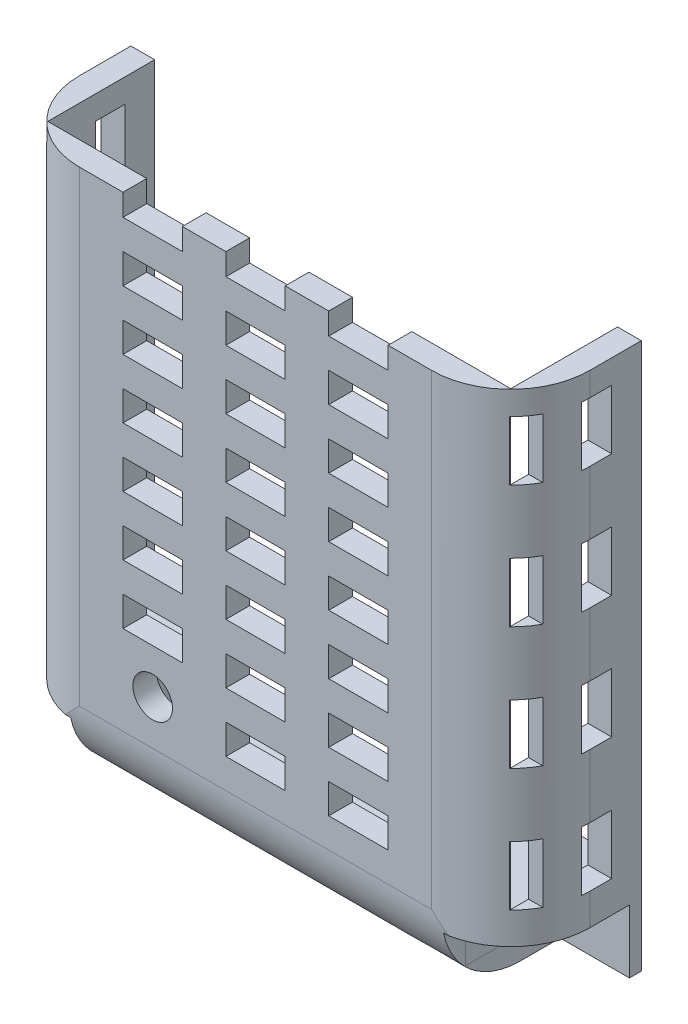
SolidWorks part; units mm, degrees
ref_plane "Plano frontal" through (0, 0, 0) normal (0, 0, 1) x (1, 0, 0)
ref_plane "Plano superior" through (0, 0, 0) normal (0, 1, 0) x (1, 0, 0)
ref_plane "Plano direito" through (0, 0, 0) normal (1, 0, 0) x (0, 0, -1)
sketch "Esboço1" plane through (0, 0, 0) normal (0, 0, 1) x (1, 0, 0)
  line L0 (-47.125, -132) -> (-47.125, -122)
  line L1 (-64.5, 138) -> (64.5, 138)
  line L2 (-64.5, 138) -> (-64.5, -138)
  line L3 (-64.5, -138) -> (64.5, -138)
  line L4 (64.5, 138) -> (64.5, -138)
  line L5 (0, -138) -> (0, 138) construction
  line L6 (-64.5, 0) -> (64.5, 0) construction
  line L7 (-58.5, 132) -> (58.5, 132) construction
  line L8 (-58.5, 132) -> (-58.5, -132) construction
  line L9 (-58.5, -132) -> (58.5, -132) construction
  line L10 (58.5, 132) -> (58.5, -132) construction
  line L11 (0, -132) -> (0, 132) construction
  line L12 (-58.5, 0) -> (58.5, 0) construction
  line L13 (-47.125, -122) -> (-58.5, -122)
  line L14 (-47, 132) -> (-47, 124.5)
  line L15 (-47, 124.5) -> (-35, 124.5)
  line L16 (-35, 124.5) -> (-35, 132)
  line L17 (-41, 130.5) -> (-41, 124.5) construction
  line L18 (-41, 130.5) -> (-35, 130.5) construction
  line L19 (-47, 132) -> (-58.5, 132)
  line L20 (-58.5, 132) -> (-58.5, -122)
  line L21 (41, 130.5) -> (35, 130.5) construction
  line L22 (41, 130.5) -> (41, 124.5) construction
  line L23 (47, 132) -> (58.5, 132)
  line L24 (35, 124.5) -> (35, 132)
  line L25 (47, 124.5) -> (35, 124.5)
  line L26 (47, 132) -> (47, 124.5)
  line L27 (58.5, 132) -> (58.5, -132) construction
  line L28 (58.5, 132) -> (58.5, -122)
  line L29 (47.125, -122) -> (58.5, -122)
  line L30 (47.125, -132) -> (47.125, -122)
  line L31 (-35, 132) -> (35, 132)
  line L32 (47.125, -132) -> (-47.125, -132)
  circle A0 centre (-53.125, -128) radius 1.6
  circle A1 centre (-41, 130.5) radius 1.6
  circle A2 centre (41, 130.5) radius 1.6
  circle A3 centre (53.125, -128) radius 1.6
  point P56 (0, 0)
  point P83 (0, 0)
  dimension "D5" = 3.2
  dimension "D8" = 3.2
  dimension "D1" = 129
  dimension "D2" = 276
  dimension "D3" = 6
  dimension "D4" = 6
  dimension "D6" = 11.375
  dimension "D7" = 10
  dimension "D9" = 23.5
  dimension "D10" = 7.5
  dimension "D11" = 6
  dimension "D12" = 6
  dimension "D13" = 6
extrude "Ressalto-extrusão1" add sketch "Esboço1" along normal blind 3
sketch "Esboço4" plane through (0, 0, 3) normal (0, 0, 1) x (1, 0, 0)
  line L0 (-64.5, 138) -> (-64.5, 72)
  line L1 (-64.5, 138) -> (-64.5, -138) construction
  line L2 (-64.5, 72) -> (-58.5, 72)
  line L3 (-58.5, 132) -> (-58.5, -122) construction
  line L4 (-58.5, 72) -> (-58.5, 132)
  line L5 (-58.5, 132) -> (-47, 132)
  line L6 (-47, 132) -> (-47, 138)
  line L7 (64.5, 138) -> (-64.5, 138) construction
  line L8 (-47, 138) -> (-64.5, 138)
  line L9 (-35, 132) -> (-35, 138)
  line L10 (-35, 138) -> (35, 138)
  line L11 (35, 138) -> (35, 132)
  line L12 (35, 132) -> (-35, 132)
  line L13 (47, 132) -> (47, 138)
  line L14 (47, 138) -> (64.5, 138)
  line L15 (64.5, 138) -> (64.5, 72)
  line L16 (64.5, -138) -> (64.5, 138) construction
  line L17 (64.5, 72) -> (58.5, 72)
  line L18 (58.5, -122) -> (58.5, 132) construction
  line L19 (58.5, 72) -> (58.5, 132)
  line L20 (58.5, 132) -> (47, 132)
  line L21 (-47.125, -132) -> (-47.125, -138)
  line L22 (-64.5, -138) -> (64.5, -138) construction
  line L23 (-47.125, -138) -> (47, -138)
  line L24 (47, -138) -> (47.125, -132)
  line L25 (47.125, -132) -> (-47.125, -132)
  line L26 (-58.5, -122) -> (-64.5, -122)
  line L27 (-64.5, -122) -> (-64.5, -22)
  line L28 (-64.5, -22) -> (-58.5, -22)
  line L29 (-58.5, -22) -> (-58.5, -122)
  line L30 (58.5, -122) -> (64.5, -122)
  line L31 (64.5, -122) -> (64.5, -22)
  line L32 (64.5, -22) -> (58.5, -22)
  line L33 (58.5, -22) -> (58.5, -122)
  dimension "D1" = 60
  dimension "D2" = 100
extrude "Ressalto-extrusão2" add sketch "Esboço4" along normal blind 24
sketch "Esboço5" plane through (0, 0, 27) normal (0, 0, 1) x (1, 0, 0)
  line L0 (-35, 132) -> (-35, 138)
  line L1 (-35, 138) -> (35, 138)
  line L2 (35, 138) -> (35, 132)
  line L3 (47, 132) -> (47, 138)
  line L4 (47, 138) -> (64.5, 138)
  line L5 (64.5, 138) -> (64.5, 72)
  line L6 (64.5, 72) -> (58.5, 72)
  line L7 (58.5, 72) -> (-64.5, 72)
  line L8 (-64.5, 72) -> (-64.5, 138)
  line L9 (-64.5, 138) -> (-47, 138)
  line L10 (-47, 138) -> (-47, 124.5)
  line L11 (-47, 124.5) -> (-35, 124.5)
  line L12 (-35, 124.5) -> (-35, 132)
  line L13 (35, 132) -> (35, 124.5)
  line L14 (35, 124.5) -> (47, 124.5)
  line L15 (47, 124.5) -> (47, 132)
  line L16 (-47.125, -138) -> (47, -138)
  line L17 (47, -138) -> (47.125, -122)
  line L18 (47.125, -122) -> (64.5, -122)
  line L19 (64.5, -122) -> (64.5, -22)
  line L20 (64.5, -22) -> (-64.5, -22)
  line L21 (-64.5, -22) -> (-64.5, -122)
  line L22 (-64.5, -122) -> (-47.125, -122)
  line L23 (-47.125, -122) -> (-47.125, -138)
extrude "Ressalto-extrusão3" add sketch "Esboço5" along normal blind 6
sketch "Esboço7" plane through (0, 0, 27) normal (0, 0, -1) x (-1, 0, 0)
  line L0 (-47, 132) -> (-53, 132)
  line L1 (-47, 132) -> (-58.5, 132) construction
  line L2 (-53, 132) -> (-53, 118.5)
  line L3 (-53, 118.5) -> (-29, 118.5)
  line L4 (-29, 118.5) -> (-29, 132)
  line L5 (35, 132) -> (-35, 132) construction
  line L6 (-29, 132) -> (-35, 132)
  line L7 (-35, 132) -> (-35, 124.5)
  line L8 (-35, 124.5) -> (-47, 124.5)
  line L9 (-47, 132) -> (-47, 124.5) construction
  line L10 (-47, 124.5) -> (-35, 124.5) construction
  line L11 (-47, 124.5) -> (-47, 132)
  line L19 (0, 0) -> (0, 50000) construction
  line L20 (58.5, -122) -> (58.5, -22) construction
  line L27 (47.125, -132) -> (47.125, -122)
  line L28 (47.125, -122) -> (58.5, -122)
  line L29 (58.5, -122) -> (58.5, -116)
  line L30 (58.5, -116) -> (41.125, -116)
  line L31 (41.125, -116) -> (41.125, -132)
  line L32 (-47.0469, -132) -> (47.125, -132) construction
  line L33 (41.125, -132) -> (47.125, -132)
  line L34 (47, 124.5) -> (47, 132)
  line L35 (35, 124.5) -> (47, 124.5)
  line L36 (35, 132) -> (35, 124.5)
  line L37 (29, 132) -> (35, 132)
  line L38 (29, 118.5) -> (29, 132)
  line L39 (53, 118.5) -> (29, 118.5)
  line L40 (53, 132) -> (53, 118.5)
  line L41 (47, 132) -> (53, 132)
  line L42 (-41.125, -132) -> (-47.125, -132)
  line L43 (-41.125, -116) -> (-41.125, -132)
  line L44 (-58.5, -116) -> (-41.125, -116)
  line L45 (-58.5, -122) -> (-58.5, -116)
  line L46 (-47.125, -122) -> (-58.5, -122)
  line L47 (-47.125, -132) -> (-47.125, -122)
  dimension "D1" = 6
  dimension "D2" = 6
  dimension "D5" = 6
extrude "Ressalto-extrusão5" add sketch "Esboço7" along normal up to vertex (27 mm away) up to point (35, 124.5, 0)
sketch "Esboço8" plane through (0, -22, 0) normal (0, 1, 0) x (1, 0, 0)
  line L0 (-58.5, -3) -> (-64.5, -3)
  line L1 (-64.5, -3) -> (-64.5, -33)
  line L2 (-64.5, -33) -> (64.5, -33)
  line L3 (64.5, -33) -> (64.5, -3)
  line L4 (64.5, -3) -> (58.5, -3)
  line L5 (58.5, -3) -> (58.5, -27)
  line L6 (58.5, -27) -> (-58.5, -27)
  line L7 (-58.5, -27) -> (-58.5, -3)
extrude "Ressalto-extrusão6" add sketch "Esboço8" along normal up to vertex (94 mm away) up to point (-58.5, 72, 27)
fillet "Filete1" radius 20 4 edges at (0, 138, 33) (-0.0625, -138, 33) (64.5, 8, 33) (-64.5, 8, 33)
sketch "Esboço9" plane through (0, 0, 33) normal (0, 0, 1) x (1, 0, 0)
  line L2 (-18.5, -106.75) -> (-7.5, -106.75) construction
  line L7 (-33.5, -103) -> (-18.5, -103) construction
  line L8 (-33.5, -103) -> (-33.5, -110.5) construction
  line L9 (-33.5, -110.5) -> (-18.5, -110.5) construction
  line L10 (-18.5, -103) -> (-18.5, -110.5) construction
  line L11 (-26, -110.5) -> (-26, -103) construction
  line L12 (-33.5, -106.75) -> (-18.5, -106.75) construction
  line L13 (-7.5, -103) -> (7.5, -103)
  line L14 (-7.5, -103) -> (-7.5, -110.5)
  line L15 (-7.5, -110.5) -> (7.5, -110.5)
  line L16 (7.5, -103) -> (7.5, -110.5)
  line L17 (0, -110.5) -> (0, -103) construction
  line L18 (-7.5, -106.75) -> (7.5, -106.75) construction
  line L19 (18.5, -103) -> (33.5, -103)
  line L20 (18.5, -103) -> (18.5, -110.5)
  line L21 (18.5, -110.5) -> (33.5, -110.5)
  line L22 (33.5, -103) -> (33.5, -110.5)
  line L23 (26, -110.5) -> (26, -103) construction
  line L24 (18.5, -106.75) -> (33.5, -106.75) construction
  line L25 (7.5, -106.75) -> (18.5, -106.75) construction
  line L26 (-33.5, -106.75) -> (-44.5, -106.75) construction
  line L27 (-44.5, 118) -> (-44.5, -118) construction
  line L28 (33.5, -106.75) -> (44.5, -106.75) construction
  line L29 (44.5, -118) -> (44.5, 118) construction
  line L30 (-44.5, -118) -> (44.5, -118) construction
  line L31 (-33.5, -88) -> (-18.5, -88)
  line L32 (-33.5, -88) -> (-33.5, -95.5)
  line L33 (-33.5, -95.5) -> (-18.5, -95.5)
  line L34 (-18.5, -88) -> (-18.5, -95.5)
  line L35 (-7.5, -88) -> (7.5, -88)
  line L36 (-7.5, -88) -> (-7.5, -95.5)
  line L37 (-7.5, -95.5) -> (7.5, -95.5)
  line L38 (7.5, -88) -> (7.5, -95.5)
  line L39 (18.5, -88) -> (33.5, -88)
  line L40 (18.5, -88) -> (18.5, -95.5)
  line L41 (18.5, -95.5) -> (33.5, -95.5)
  line L42 (33.5, -88) -> (33.5, -95.5)
  line L43 (-18.5, -91.75) -> (-7.5, -91.75) construction
  line L44 (-26, -95.5) -> (-26, -88) construction
  line L45 (-33.5, -91.75) -> (-18.5, -91.75) construction
  line L46 (0, -95.5) -> (0, -88) construction
  line L47 (-7.5, -91.75) -> (7.5, -91.75) construction
  line L48 (26, -95.5) -> (26, -88) construction
  line L49 (18.5, -91.75) -> (33.5, -91.75) construction
  line L50 (7.5, -91.75) -> (18.5, -91.75) construction
  line L51 (-33.5, -73) -> (-18.5, -73)
  line L52 (-33.5, -73) -> (-33.5, -80.5)
  line L53 (-33.5, -80.5) -> (-18.5, -80.5)
  line L54 (-18.5, -73) -> (-18.5, -80.5)
  line L55 (-7.5, -73) -> (7.5, -73)
  line L56 (-7.5, -73) -> (-7.5, -80.5)
  line L57 (-7.5, -80.5) -> (7.5, -80.5)
  line L58 (7.5, -73) -> (7.5, -80.5)
  line L59 (18.5, -73) -> (33.5, -73)
  line L60 (18.5, -73) -> (18.5, -80.5)
  line L61 (18.5, -80.5) -> (33.5, -80.5)
  line L62 (33.5, -73) -> (33.5, -80.5)
  line L63 (-18.5, -76.75) -> (-7.5, -76.75) construction
  line L64 (-26, -80.5) -> (-26, -73) construction
  line L65 (-33.5, -76.75) -> (-18.5, -76.75) construction
  line L66 (0, -80.5) -> (0, -73) construction
  line L67 (-7.5, -76.75) -> (7.5, -76.75) construction
  line L68 (26, -80.5) -> (26, -73) construction
  line L69 (18.5, -76.75) -> (33.5, -76.75) construction
  line L70 (7.5, -76.75) -> (18.5, -76.75) construction
  line L71 (-33.5, -58) -> (-18.5, -58)
  line L72 (-33.5, -58) -> (-33.5, -65.5)
  line L73 (-33.5, -65.5) -> (-18.5, -65.5)
  line L74 (-18.5, -58) -> (-18.5, -65.5)
  line L75 (-7.5, -58) -> (7.5, -58)
  line L76 (-7.5, -58) -> (-7.5, -65.5)
  line L77 (-7.5, -65.5) -> (7.5, -65.5)
  line L78 (7.5, -58) -> (7.5, -65.5)
  line L79 (18.5, -58) -> (33.5, -58)
  line L80 (18.5, -58) -> (18.5, -65.5)
  line L81 (18.5, -65.5) -> (33.5, -65.5)
  line L82 (33.5, -58) -> (33.5, -65.5)
  line L83 (-18.5, -61.75) -> (-7.5, -61.75) construction
  line L84 (-26, -65.5) -> (-26, -58) construction
  line L85 (-33.5, -61.75) -> (-18.5, -61.75) construction
  line L86 (0, -65.5) -> (0, -58) construction
  line L87 (-7.5, -61.75) -> (7.5, -61.75) construction
  line L88 (26, -65.5) -> (26, -58) construction
  line L89 (18.5, -61.75) -> (33.5, -61.75) construction
  line L90 (7.5, -61.75) -> (18.5, -61.75) construction
  line L91 (-33.5, -43) -> (-18.5, -43)
  line L92 (-33.5, -43) -> (-33.5, -50.5)
  line L93 (-33.5, -50.5) -> (-18.5, -50.5)
  line L94 (-18.5, -43) -> (-18.5, -50.5)
  line L95 (-7.5, -43) -> (7.5, -43)
  line L96 (-7.5, -43) -> (-7.5, -50.5)
  line L97 (-7.5, -50.5) -> (7.5, -50.5)
  line L98 (7.5, -43) -> (7.5, -50.5)
  line L99 (18.5, -43) -> (33.5, -43)
  line L100 (18.5, -43) -> (18.5, -50.5)
  line L101 (18.5, -50.5) -> (33.5, -50.5)
  line L102 (33.5, -43) -> (33.5, -50.5)
  line L103 (-18.5, -46.75) -> (-7.5, -46.75) construction
  line L104 (-26, -50.5) -> (-26, -43) construction
  line L105 (-33.5, -46.75) -> (-18.5, -46.75) construction
  line L106 (0, -50.5) -> (0, -43) construction
  line L107 (-7.5, -46.75) -> (7.5, -46.75) construction
  line L108 (26, -50.5) -> (26, -43) construction
  line L109 (18.5, -46.75) -> (33.5, -46.75) construction
  line L110 (7.5, -46.75) -> (18.5, -46.75) construction
  line L111 (-33.5, -28) -> (-18.5, -28)
  line L112 (-33.5, -28) -> (-33.5, -35.5)
  line L113 (-33.5, -35.5) -> (-18.5, -35.5)
  line L114 (-18.5, -28) -> (-18.5, -35.5)
  line L115 (-7.5, -28) -> (7.5, -28)
  line L116 (-7.5, -28) -> (-7.5, -35.5)
  line L117 (-7.5, -35.5) -> (7.5, -35.5)
  line L118 (7.5, -28) -> (7.5, -35.5)
  line L119 (18.5, -28) -> (33.5, -28)
  line L120 (18.5, -28) -> (18.5, -35.5)
  line L121 (18.5, -35.5) -> (33.5, -35.5)
  line L122 (33.5, -28) -> (33.5, -35.5)
  line L123 (-18.5, -31.75) -> (-7.5, -31.75) construction
  line L124 (-26, -35.5) -> (-26, -28) construction
  line L125 (-33.5, -31.75) -> (-18.5, -31.75) construction
  line L126 (0, -35.5) -> (0, -28) construction
  line L127 (-7.5, -31.75) -> (7.5, -31.75) construction
  line L128 (26, -35.5) -> (26, -28) construction
  line L129 (18.5, -31.75) -> (33.5, -31.75) construction
  line L130 (7.5, -31.75) -> (18.5, -31.75) construction
  line L131 (-33.5, -13) -> (-18.5, -13)
  line L132 (-33.5, -13) -> (-33.5, -20.5)
  line L133 (-33.5, -20.5) -> (-18.5, -20.5)
  line L134 (-18.5, -13) -> (-18.5, -20.5)
  line L135 (-7.5, -13) -> (7.5, -13)
  line L136 (-7.5, -13) -> (-7.5, -20.5)
  line L137 (-7.5, -20.5) -> (7.5, -20.5)
  line L138 (7.5, -13) -> (7.5, -20.5)
  line L139 (18.5, -13) -> (33.5, -13)
  line L140 (18.5, -13) -> (18.5, -20.5)
  line L141 (18.5, -20.5) -> (33.5, -20.5)
  line L142 (33.5, -13) -> (33.5, -20.5)
  line L143 (-18.5, -16.75) -> (-7.5, -16.75) construction
  line L144 (-26, -20.5) -> (-26, -13) construction
  line L145 (-33.5, -16.75) -> (-18.5, -16.75) construction
  line L146 (0, -20.5) -> (0, -13) construction
  line L147 (-7.5, -16.75) -> (7.5, -16.75) construction
  line L148 (26, -20.5) -> (26, -13) construction
  line L149 (18.5, -16.75) -> (33.5, -16.75) construction
  line L150 (7.5, -16.75) -> (18.5, -16.75) construction
  line L151 (-33.5, 2) -> (-18.5, 2)
  line L152 (-33.5, 2) -> (-33.5, -5.5)
  line L153 (-33.5, -5.5) -> (-18.5, -5.5)
  line L154 (-18.5, 2) -> (-18.5, -5.5)
  line L155 (-7.5, 2) -> (7.5, 2)
  line L156 (-7.5, 2) -> (-7.5, -5.5)
  line L157 (-7.5, -5.5) -> (7.5, -5.5)
  line L158 (7.5, 2) -> (7.5, -5.5)
  line L159 (18.5, 2) -> (33.5, 2)
  line L160 (18.5, 2) -> (18.5, -5.5)
  line L161 (18.5, -5.5) -> (33.5, -5.5)
  line L162 (33.5, 2) -> (33.5, -5.5)
  line L163 (-18.5, -1.75) -> (-7.5, -1.75) construction
  line L164 (-26, -5.5) -> (-26, 2) construction
  line L165 (-33.5, -1.75) -> (-18.5, -1.75) construction
  line L166 (0, -5.5) -> (0, 2) construction
  line L167 (-7.5, -1.75) -> (7.5, -1.75) construction
  line L168 (26, -5.5) -> (26, 2) construction
  line L169 (18.5, -1.75) -> (33.5, -1.75) construction
  line L170 (7.5, -1.75) -> (18.5, -1.75) construction
  line L171 (-33.5, 17) -> (-18.5, 17)
  line L172 (-33.5, 17) -> (-33.5, 9.5)
  line L173 (-33.5, 9.5) -> (-18.5, 9.5)
  line L174 (-18.5, 17) -> (-18.5, 9.5)
  line L175 (-7.5, 17) -> (7.5, 17)
  line L176 (-7.5, 17) -> (-7.5, 9.5)
  line L177 (-7.5, 9.5) -> (7.5, 9.5)
  line L178 (7.5, 17) -> (7.5, 9.5)
  line L179 (18.5, 17) -> (33.5, 17)
  line L180 (18.5, 17) -> (18.5, 9.5)
  line L181 (18.5, 9.5) -> (33.5, 9.5)
  line L182 (33.5, 17) -> (33.5, 9.5)
  line L183 (-18.5, 13.25) -> (-7.5, 13.25) construction
  line L184 (-26, 9.5) -> (-26, 17) construction
  line L185 (-33.5, 13.25) -> (-18.5, 13.25) construction
  line L186 (0, 9.5) -> (0, 17) construction
  line L187 (-7.5, 13.25) -> (7.5, 13.25) construction
  line L188 (26, 9.5) -> (26, 17) construction
  line L189 (18.5, 13.25) -> (33.5, 13.25) construction
  line L190 (7.5, 13.25) -> (18.5, 13.25) construction
  line L191 (-33.5, 32) -> (-18.5, 32)
  line L192 (-33.5, 32) -> (-33.5, 24.5)
  line L193 (-33.5, 24.5) -> (-18.5, 24.5)
  line L194 (-18.5, 32) -> (-18.5, 24.5)
  line L195 (-7.5, 32) -> (7.5, 32)
  line L196 (-7.5, 32) -> (-7.5, 24.5)
  line L197 (-7.5, 24.5) -> (7.5, 24.5)
  line L198 (7.5, 32) -> (7.5, 24.5)
  line L199 (18.5, 32) -> (33.5, 32)
  line L200 (18.5, 32) -> (18.5, 24.5)
  line L201 (18.5, 24.5) -> (33.5, 24.5)
  line L202 (33.5, 32) -> (33.5, 24.5)
  line L203 (-18.5, 28.25) -> (-7.5, 28.25) construction
  line L204 (-26, 24.5) -> (-26, 32) construction
  line L205 (-33.5, 28.25) -> (-18.5, 28.25) construction
  line L206 (0, 24.5) -> (0, 32) construction
  line L207 (-7.5, 28.25) -> (7.5, 28.25) construction
  line L208 (26, 24.5) -> (26, 32) construction
  line L209 (18.5, 28.25) -> (33.5, 28.25) construction
  line L210 (7.5, 28.25) -> (18.5, 28.25) construction
  line L211 (-33.5, 47) -> (-18.5, 47)
  line L212 (-33.5, 47) -> (-33.5, 39.5)
  line L213 (-33.5, 39.5) -> (-18.5, 39.5)
  line L214 (-18.5, 47) -> (-18.5, 39.5)
  line L215 (-7.5, 47) -> (7.5, 47)
  line L216 (-7.5, 47) -> (-7.5, 39.5)
  line L217 (-7.5, 39.5) -> (7.5, 39.5)
  line L218 (7.5, 47) -> (7.5, 39.5)
  line L219 (18.5, 47) -> (33.5, 47)
  line L220 (18.5, 47) -> (18.5, 39.5)
  line L221 (18.5, 39.5) -> (33.5, 39.5)
  line L222 (33.5, 47) -> (33.5, 39.5)
  line L223 (-18.5, 43.25) -> (-7.5, 43.25) construction
  line L224 (-26, 39.5) -> (-26, 47) construction
  line L225 (-33.5, 43.25) -> (-18.5, 43.25) construction
  line L226 (0, 39.5) -> (0, 47) construction
  line L227 (-7.5, 43.25) -> (7.5, 43.25) construction
  line L228 (26, 39.5) -> (26, 47) construction
  line L229 (18.5, 43.25) -> (33.5, 43.25) construction
  line L230 (7.5, 43.25) -> (18.5, 43.25) construction
  line L231 (-33.5, 62) -> (-18.5, 62)
  line L232 (-33.5, 62) -> (-33.5, 54.5)
  line L233 (-33.5, 54.5) -> (-18.5, 54.5)
  line L234 (-18.5, 62) -> (-18.5, 54.5)
  line L235 (-7.5, 62) -> (7.5, 62)
  line L236 (-7.5, 62) -> (-7.5, 54.5)
  line L237 (-7.5, 54.5) -> (7.5, 54.5)
  line L238 (7.5, 62) -> (7.5, 54.5)
  line L239 (18.5, 62) -> (33.5, 62)
  line L240 (18.5, 62) -> (18.5, 54.5)
  line L241 (18.5, 54.5) -> (33.5, 54.5)
  line L242 (33.5, 62) -> (33.5, 54.5)
  line L243 (-18.5, 58.25) -> (-7.5, 58.25) construction
  line L244 (-26, 54.5) -> (-26, 62) construction
  line L245 (-33.5, 58.25) -> (-18.5, 58.25) construction
  line L246 (0, 54.5) -> (0, 62) construction
  line L247 (-7.5, 58.25) -> (7.5, 58.25) construction
  line L248 (26, 54.5) -> (26, 62) construction
  line L249 (18.5, 58.25) -> (33.5, 58.25) construction
  line L250 (7.5, 58.25) -> (18.5, 58.25) construction
  line L251 (-33.5, 77) -> (-18.5, 77)
  line L252 (-33.5, 77) -> (-33.5, 69.5)
  line L253 (-33.5, 69.5) -> (-18.5, 69.5)
  line L254 (-18.5, 77) -> (-18.5, 69.5)
  line L255 (-7.5, 77) -> (7.5, 77)
  line L256 (-7.5, 77) -> (-7.5, 69.5)
  line L257 (-7.5, 69.5) -> (7.5, 69.5)
  line L258 (7.5, 77) -> (7.5, 69.5)
  line L259 (18.5, 77) -> (33.5, 77)
  line L260 (18.5, 77) -> (18.5, 69.5)
  line L261 (18.5, 69.5) -> (33.5, 69.5)
  line L262 (33.5, 77) -> (33.5, 69.5)
  line L263 (-18.5, 73.25) -> (-7.5, 73.25) construction
  line L264 (-26, 69.5) -> (-26, 77) construction
  line L265 (-33.5, 73.25) -> (-18.5, 73.25) construction
  line L266 (0, 69.5) -> (0, 77) construction
  line L267 (-7.5, 73.25) -> (7.5, 73.25) construction
  line L268 (26, 69.5) -> (26, 77) construction
  line L269 (18.5, 73.25) -> (33.5, 73.25) construction
  line L270 (7.5, 73.25) -> (18.5, 73.25) construction
  line L271 (-33.5, 92) -> (-18.5, 92)
  line L272 (-33.5, 92) -> (-33.5, 84.5)
  line L273 (-33.5, 84.5) -> (-18.5, 84.5)
  line L274 (-18.5, 92) -> (-18.5, 84.5)
  line L275 (-7.5, 92) -> (7.5, 92)
  line L276 (-7.5, 92) -> (-7.5, 84.5)
  line L277 (-7.5, 84.5) -> (7.5, 84.5)
  line L278 (7.5, 92) -> (7.5, 84.5)
  line L279 (18.5, 92) -> (33.5, 92)
  line L280 (18.5, 92) -> (18.5, 84.5)
  line L281 (18.5, 84.5) -> (33.5, 84.5)
  line L282 (33.5, 92) -> (33.5, 84.5)
  line L283 (-18.5, 88.25) -> (-7.5, 88.25) construction
  line L284 (-26, 84.5) -> (-26, 92) construction
  line L285 (-33.5, 88.25) -> (-18.5, 88.25) construction
  line L286 (0, 84.5) -> (0, 92) construction
  line L287 (-7.5, 88.25) -> (7.5, 88.25) construction
  line L288 (26, 84.5) -> (26, 92) construction
  line L289 (18.5, 88.25) -> (33.5, 88.25) construction
  line L290 (7.5, 88.25) -> (18.5, 88.25) construction
  line L291 (-33.5, 107) -> (-18.5, 107)
  line L292 (-33.5, 107) -> (-33.5, 99.5)
  line L293 (-33.5, 99.5) -> (-18.5, 99.5)
  line L294 (-18.5, 107) -> (-18.5, 99.5)
  line L295 (-7.5, 107) -> (7.5, 107)
  line L296 (-7.5, 107) -> (-7.5, 99.5)
  line L297 (-7.5, 99.5) -> (7.5, 99.5)
  line L298 (7.5, 107) -> (7.5, 99.5)
  line L299 (18.5, 107) -> (33.5, 107)
  line L300 (18.5, 107) -> (18.5, 99.5)
  line L301 (18.5, 99.5) -> (33.5, 99.5)
  line L302 (33.5, 107) -> (33.5, 99.5)
  line L303 (-18.5, 103.25) -> (-7.5, 103.25) construction
  line L304 (-26, 99.5) -> (-26, 107) construction
  line L305 (-33.5, 103.25) -> (-18.5, 103.25) construction
  line L306 (0, 99.5) -> (0, 107) construction
  line L307 (-7.5, 103.25) -> (7.5, 103.25) construction
  line L308 (26, 99.5) -> (26, 107) construction
  line L309 (18.5, 103.25) -> (33.5, 103.25) construction
  line L310 (7.5, 103.25) -> (18.5, 103.25) construction
  circle A1 centre (-26, -106.75) radius 5
  point P38 (0, -91.75)
  point P43 (26, -91.75)
  point P48 (-26, -91.75)
  point P65 (0, -76.75)
  point P70 (26, -76.75)
  point P75 (-26, -76.75)
  point P92 (0, -61.75)
  point P97 (26, -61.75)
  point P102 (-26, -61.75)
  point P112 (0, -106.75)
  point P123 (0, -46.75)
  point P128 (26, -46.75)
  point P133 (-26, -46.75)
  point P145 (26, -106.75)
  point P155 (0, -31.75)
  point P160 (26, -31.75)
  point P165 (-26, -31.75)
  point P180 (-26, -106.75)
  point P187 (0, -16.75)
  point P192 (26, -16.75)
  point P197 (-26, -16.75)
  point P214 (0, -1.75)
  point P219 (26, -1.75)
  point P224 (-26, -1.75)
  point P241 (0, 13.25)
  point P246 (26, 13.25)
  point P251 (-26, 13.25)
  point P268 (0, 28.25)
  point P273 (26, 28.25)
  point P278 (-26, 28.25)
  point P295 (0, 43.25)
  point P300 (26, 43.25)
  point P305 (-26, 43.25)
  point P322 (0, 58.25)
  point P327 (26, 58.25)
  point P332 (-26, 58.25)
  point P349 (0, 73.25)
  point P354 (26, 73.25)
  point P359 (-26, 73.25)
  point P376 (0, 88.25)
  point P381 (26, 88.25)
  point P386 (-26, 88.25)
  point P403 (0, 103.25)
  point P408 (26, 103.25)
  point P413 (-26, 103.25)
  dimension "D1" = 15
  dimension "D5" = 10
  dimension "D2" = 7.5
  dimension "D3" = 7.5
  dimension "D4" = 15
extrude "Corte-extrusão1" cut sketch "Esboço9" against normal up to next (6 mm away)
sketch "Esboço10" plane through (0, -138, 0) normal (0, -1, 0) x (1, 0, 0)
  line L0 (47, 13) -> (-47.125, 13) construction
  line L1 (-39.625, 28) -> (-24.625, 28)
  line L2 (-39.625, 28) -> (-39.625, 20.5)
  line L3 (-39.625, 20.5) -> (-24.625, 20.5)
  line L4 (-24.625, 28) -> (-24.625, 20.5)
  line L5 (-32.125, 20.5) -> (-32.125, 28) construction
  line L6 (-39.625, 24.25) -> (-24.625, 24.25) construction
  line L7 (-47.125, 32.5959) -> (-47.125, 13) construction
  line L8 (-9.625, 28) -> (5.375, 28)
  line L9 (-9.625, 28) -> (-9.625, 20.5)
  line L10 (-9.625, 20.5) -> (5.375, 20.5)
  line L11 (5.375, 28) -> (5.375, 20.5)
  line L12 (-2.125, 20.5) -> (-2.125, 28) construction
  line L13 (-9.625, 24.25) -> (5.375, 24.25) construction
  line L14 (20.375, 28) -> (35.375, 28)
  line L15 (20.375, 28) -> (20.375, 20.5)
  line L16 (20.375, 20.5) -> (35.375, 20.5)
  line L17 (35.375, 28) -> (35.375, 20.5)
  line L18 (27.875, 20.5) -> (27.875, 28) construction
  line L19 (20.375, 24.25) -> (35.375, 24.25) construction
  line L20 (-39.625, 15.5) -> (-24.625, 15.5)
  line L21 (-39.625, 15.5) -> (-39.625, 8)
  line L22 (-39.625, 8) -> (-24.625, 8)
  line L23 (-24.625, 15.5) -> (-24.625, 8)
  line L24 (-9.625, 15.5) -> (5.375, 15.5)
  line L25 (-9.625, 15.5) -> (-9.625, 8)
  line L26 (-9.625, 8) -> (5.375, 8)
  line L27 (5.375, 15.5) -> (5.375, 8)
  line L28 (20.375, 15.5) -> (35.375, 15.5)
  line L29 (20.375, 15.5) -> (20.375, 8)
  line L30 (20.375, 8) -> (35.375, 8)
  line L31 (35.375, 15.5) -> (35.375, 8)
  line L32 (-32.125, 8) -> (-32.125, 15.5) construction
  line L33 (-39.625, 11.75) -> (-24.625, 11.75) construction
  line L34 (-2.125, 8) -> (-2.125, 15.5) construction
  line L35 (-9.625, 11.75) -> (5.375, 11.75) construction
  line L36 (27.875, 8) -> (27.875, 15.5) construction
  line L37 (20.375, 11.75) -> (35.375, 11.75) construction
  point P17 (-2.125, 24.25)
  point P26 (27.875, 24.25)
  point P39 (-2.125, 11.75)
  point P48 (27.875, 11.75)
  point P53 (-32.125, 11.75)
  point P132 (-32.125, 24.25)
  dimension "D1" = 15
  dimension "D2" = 7.5
  dimension "D3" = 7.5
  dimension "D4" = 7.5
  dimension "D5" = 3
  dimension "D6" = 2
extrude "Corte-extrusão2" cut sketch "Esboço10" against normal up to vertex (6 mm away) up to point (41.125, -132, 27)
sketch "Esboço11" plane through (0, 138, 0) normal (0, 1, 0) x (1, 0, 0)
  line L0 (44.5, -33) -> (-44.5, -33) construction
  line L1 (-28.8651, -18) -> (-13.8651, -18)
  line L2 (-28.8651, -18) -> (-28.8651, -25.5)
  line L3 (-28.8651, -25.5) -> (-13.8651, -25.5)
  line L4 (-13.8651, -18) -> (-13.8651, -25.5)
  line L5 (-21.3651, -25.5) -> (-21.3651, -18) construction
  line L6 (-28.8651, -21.75) -> (-13.8651, -21.75) construction
  line L7 (-8.8651, -18) -> (6.1349, -18)
  line L8 (-8.8651, -18) -> (-8.8651, -25.5)
  line L9 (-8.8651, -25.5) -> (6.1349, -25.5)
  line L10 (6.1349, -18) -> (6.1349, -25.5)
  line L11 (-1.3651, -25.5) -> (-1.3651, -18) construction
  line L12 (-8.8651, -21.75) -> (6.1349, -21.75) construction
  line L13 (11.1349, -18) -> (26.1349, -18)
  line L14 (11.1349, -18) -> (11.1349, -25.5)
  line L15 (11.1349, -25.5) -> (26.1349, -25.5)
  line L16 (26.1349, -18) -> (26.1349, -25.5)
  line L17 (18.6349, -25.5) -> (18.6349, -18) construction
  line L18 (11.1349, -21.75) -> (26.1349, -21.75) construction
  line L19 (-8.8651, -3) -> (6.1349, -3)
  line L20 (-8.8651, -3) -> (-8.8651, -10.5)
  line L21 (-8.8651, -10.5) -> (6.1349, -10.5)
  line L22 (6.1349, -3) -> (6.1349, -10.5)
  line L23 (-1.3651, -10.5) -> (-1.3651, -3) construction
  line L24 (-8.8651, -6.75) -> (6.1349, -6.75) construction
  line L25 (11.1349, -3) -> (26.1349, -3)
  line L26 (11.1349, -3) -> (11.1349, -10.5)
  line L27 (11.1349, -10.5) -> (26.1349, -10.5)
  line L28 (26.1349, -3) -> (26.1349, -10.5)
  line L29 (18.6349, -10.5) -> (18.6349, -3) construction
  line L30 (11.1349, -6.75) -> (26.1349, -6.75) construction
  line L31 (-28.8651, -3) -> (-13.8651, -3)
  line L32 (-28.8651, -3) -> (-28.8651, -10.5)
  line L33 (-28.8651, -10.5) -> (-13.8651, -10.5)
  line L34 (-13.8651, -3) -> (-13.8651, -10.5)
  line L35 (-21.3651, -10.5) -> (-21.3651, -3) construction
  line L36 (-28.8651, -6.75) -> (-13.8651, -6.75) construction
  point P16 (-1.3651, -21.75)
  point P28 (-21.3651, -21.75)
  point P30 (18.6349, -21.75)
  point P39 (-1.3651, -6.75)
  point P48 (18.6349, -6.75)
  point P57 (-21.3651, -6.75)
  dimension "D1" = 7.5
  dimension "D2" = 15
  dimension "D3" = 7.5
  dimension "D4" = 3
  dimension "D5" = 2
extrude "Corte-extrusão3" cut sketch "Esboço11" against normal up to vertex (6 mm away) up to point (-29, 132, 27)
sketch "Esboço12" plane through (-64.5, 0, 0) normal (-1, 0, 0) x (0, 0, 1)
  line L0 (15, 118) -> (33, 118) construction
  line L1 (7.5, 118) -> (15, 118)
  line L2 (7.5, 118) -> (7.5, 103)
  line L3 (7.5, 103) -> (15, 103)
  line L4 (15, 118) -> (15, 103)
  line L5 (11.25, 103) -> (11.25, 118) construction
  line L6 (7.5, 110.5) -> (15, 110.5) construction
  line L7 (0, 138) -> (0, -138) construction
  line L8 (22.5, 118) -> (30, 118)
  line L9 (22.5, 118) -> (22.5, 103)
  line L10 (22.5, 103) -> (30, 103)
  line L11 (30, 118) -> (30, 103)
  line L12 (26.25, 103) -> (26.25, 118) construction
  line L13 (22.5, 110.5) -> (30, 110.5) construction
  line L14 (22.5, 87) -> (30, 87)
  line L15 (22.5, 87) -> (22.5, 72)
  line L16 (22.5, 72) -> (30, 72)
  line L17 (30, 87) -> (30, 72)
  line L18 (26.25, 72) -> (26.25, 87) construction
  line L19 (22.5, 79.5) -> (30, 79.5) construction
  line L20 (22.5, 56) -> (30, 56)
  line L21 (22.5, 56) -> (22.5, 41)
  line L22 (22.5, 41) -> (30, 41)
  line L23 (30, 56) -> (30, 41)
  line L24 (26.25, 41) -> (26.25, 56) construction
  line L25 (22.5, 48.5) -> (30, 48.5) construction
  line L26 (22.5, 25) -> (30, 25)
  line L27 (22.5, 25) -> (22.5, 10)
  line L28 (22.5, 10) -> (30, 10)
  line L29 (30, 25) -> (30, 10)
  line L30 (26.25, 10) -> (26.25, 25) construction
  line L31 (22.5, 17.5) -> (30, 17.5) construction
  line L32 (22.5, -6) -> (30, -6)
  line L33 (22.5, -6) -> (22.5, -21)
  line L34 (22.5, -21) -> (30, -21)
  line L35 (30, -6) -> (30, -21)
  line L36 (26.25, -21) -> (26.25, -6) construction
  line L37 (22.5, -13.5) -> (30, -13.5) construction
  line L38 (22.5, -37) -> (30, -37)
  line L39 (22.5, -37) -> (22.5, -52)
  line L40 (22.5, -52) -> (30, -52)
  line L41 (30, -37) -> (30, -52)
  line L42 (26.25, -52) -> (26.25, -37) construction
  line L43 (22.5, -44.5) -> (30, -44.5) construction
  line L44 (22.5, -68) -> (30, -68)
  line L45 (22.5, -68) -> (22.5, -83)
  line L46 (22.5, -83) -> (30, -83)
  line L47 (30, -68) -> (30, -83)
  line L48 (26.25, -83) -> (26.25, -68) construction
  line L49 (22.5, -75.5) -> (30, -75.5) construction
  line L50 (22.5, -99) -> (30, -99)
  line L51 (22.5, -99) -> (22.5, -114)
  line L52 (22.5, -114) -> (30, -114)
  line L53 (30, -99) -> (30, -114)
  line L54 (26.25, -114) -> (26.25, -99) construction
  line L55 (22.5, -106.5) -> (30, -106.5) construction
  line L56 (7.5, 87) -> (15, 87)
  line L57 (7.5, 87) -> (7.5, 72)
  line L58 (7.5, 72) -> (15, 72)
  line L59 (15, 87) -> (15, 72)
  line L60 (11.25, 72) -> (11.25, 87) construction
  line L61 (7.5, 79.5) -> (15, 79.5) construction
  line L62 (7.5, 56) -> (15, 56)
  line L63 (7.5, 56) -> (7.5, 41)
  line L64 (7.5, 41) -> (15, 41)
  line L65 (15, 56) -> (15, 41)
  line L66 (11.25, 41) -> (11.25, 56) construction
  line L67 (7.5, 48.5) -> (15, 48.5) construction
  line L68 (7.5, 25) -> (15, 25)
  line L69 (7.5, 25) -> (7.5, 10)
  line L70 (7.5, 10) -> (15, 10)
  line L71 (15, 25) -> (15, 10)
  line L72 (11.25, 10) -> (11.25, 25) construction
  line L73 (7.5, 17.5) -> (15, 17.5) construction
  line L74 (7.5, -6) -> (15, -6)
  line L75 (7.5, -6) -> (7.5, -21)
  line L76 (7.5, -21) -> (15, -21)
  line L77 (15, -6) -> (15, -21)
  line L78 (11.25, -21) -> (11.25, -6) construction
  line L79 (7.5, -13.5) -> (15, -13.5) construction
  line L80 (7.5, -37) -> (15, -37)
  line L81 (7.5, -37) -> (7.5, -52)
  line L82 (7.5, -52) -> (15, -52)
  line L83 (15, -37) -> (15, -52)
  line L84 (11.25, -52) -> (11.25, -37) construction
  line L85 (7.5, -44.5) -> (15, -44.5) construction
  line L86 (7.5, -68) -> (15, -68)
  line L87 (7.5, -68) -> (7.5, -83)
  line L88 (7.5, -83) -> (15, -83)
  line L89 (15, -68) -> (15, -83)
  line L90 (11.25, -83) -> (11.25, -68) construction
  line L91 (7.5, -75.5) -> (15, -75.5) construction
  line L92 (7.5, -99) -> (15, -99)
  line L93 (7.5, -99) -> (7.5, -114)
  line L94 (7.5, -114) -> (15, -114)
  line L95 (15, -99) -> (15, -114)
  line L96 (11.25, -114) -> (11.25, -99) construction
  line L97 (7.5, -106.5) -> (15, -106.5) construction
  point P17 (26.25, 110.5)
  point P26 (26.25, 79.5)
  point P35 (26.25, 48.5)
  point P44 (26.25, 17.5)
  point P53 (26.25, -13.5)
  point P62 (26.25, -44.5)
  point P71 (26.25, -75.5)
  point P80 (26.25, -106.5)
  point P89 (11.25, 79.5)
  point P100 (11.25, 110.5)
  point P104 (11.25, 48.5)
  point P113 (11.25, 17.5)
  point P122 (11.25, -13.5)
  point P131 (11.25, -44.5)
  point P140 (11.25, -75.5)
  point P149 (11.25, -106.5)
  dimension "D1" = 15
  dimension "D2" = 7.5
  dimension "D3" = 7.5
  dimension "D4" = 2
  dimension "D5" = 8
extrude "Corte-extrusão4" cut sketch "Esboço12" against normal up to vertex (6 mm away) up to point (-58.5, -116, 27)
mirror "Espelhar2" about plane through (0, 0, 0) normal (1, 0, 0) of "Corte-extrusão4"
sketch "Esboço13" plane through (0, 0, 33) normal (0, 0, 1) x (1, 0, 0)
  line L5 (-64.5, -6) -> (-64.5, 10) construction
  line L6 (-64.5, 0) -> (64.5, 0)
  line L8 (-64.5, 0) -> (-64.5, 138)
  line L9 (-64.5, 138) -> (64.5, 138)
  line L10 (64.5, 0) -> (64.5, 138)
  line L11 (0, 138) -> (0, 0) construction
  line L12 (-64.5, 69) -> (64.5, 69) construction
  point P372 (0, 69)
extrude "Corte-extrusão5" cut sketch "Esboço13" against normal up to vertex (33 mm away) up to point (-58.5, -116, 0)
